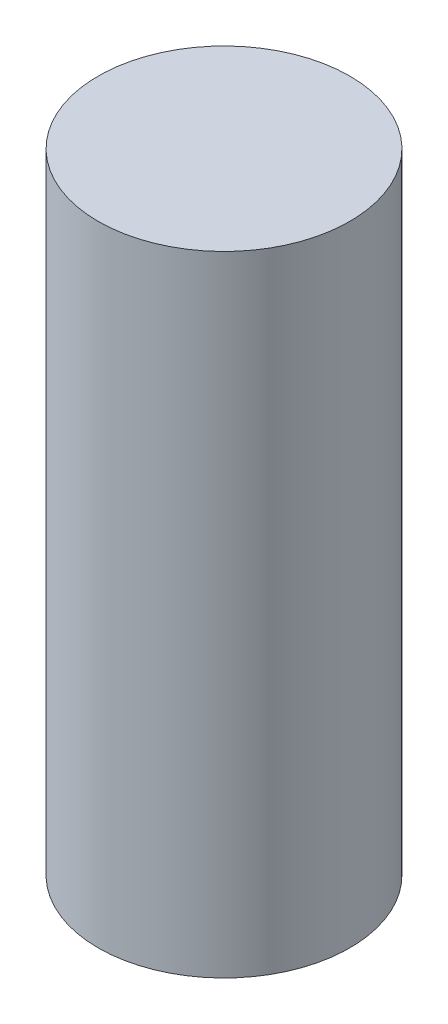
SolidWorks part; units mm, degrees
ref_plane "Front Plane" through (0, 0, 0) normal (0, 0, 1) x (1, 0, 0)
ref_plane "Top Plane" through (0, 0, 0) normal (0, 1, 0) x (1, 0, 0)
ref_plane "Right Plane" through (0, 0, 0) normal (1, 0, 0) x (0, 0, -1)
ref_axis "Axis1" through (0, 105, 0) along (0, -1, 0)
sketch "Sketch1" plane through (0, 0, 0) normal (0, 1, 0) x (1, 0, 0)
  circle A0 centre (0, 0) radius 20
  dimension "D1" = 40
extrude "Boss-Extrude1" add sketch "Sketch1" along normal blind 100
ref_plane "Plane1" through (0, 50, 0) normal (0, -1, 0) x (-1, 0, 0)
ref_axis "Axis2" through (0, 50, 22) along (0, 0, -1)
